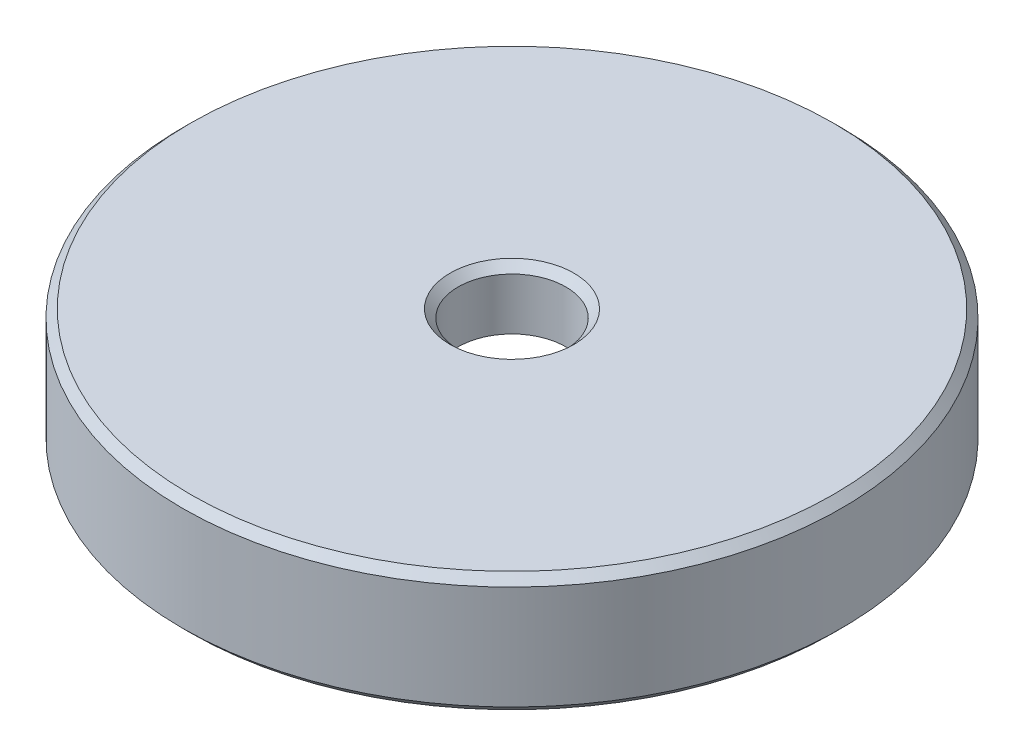
SolidWorks part; units mm, degrees
ref_plane "Front Plane" through (0, 0, 0) normal (0, 0, 1) x (1, 0, 0)
ref_plane "Top Plane" through (0, 0, 0) normal (0, 1, 0) x (1, 0, 0)
ref_plane "Right Plane" through (0, 0, 0) normal (1, 0, 0) x (0, 0, -1)
sketch "Sketch1" plane through (0, 0, 0) normal (0, 1, 0) x (1, 0, 0)
  circle A0 centre (0, 0) radius 16.5
  circle A1 centre (0, 0) radius 14.7
  circle A2 centre (0, 0) radius 2.7
  dimension "D1" = 29.4
  dimension "D2" = 33
  dimension "D3" = 5.4
extrude "Boss-Extrude1" add sketch "Sketch1" along normal blind 3 contours A0 A1 | A1 A2 region at (-16.0333, 0, 0) region at (-14.2842, 0, 0)
extrude "Boss-Extrude2" add sketch "Sketch1<3>" against normal blind 3 contours A0 A1 region at (-16.0333, 0, 0)
sketch "Sketch1<3>" plane through (0, 0, 0) normal (0, 1, 0) x (1, 0, 0) same geometry as "Sketch1"
chamfer "Chamfer1" distance 0.4 angle 45 4 edges at (0, -3, 14.7) (0, -3, 16.5) (0, 3, 16.5) (0, 3, 2.7)
